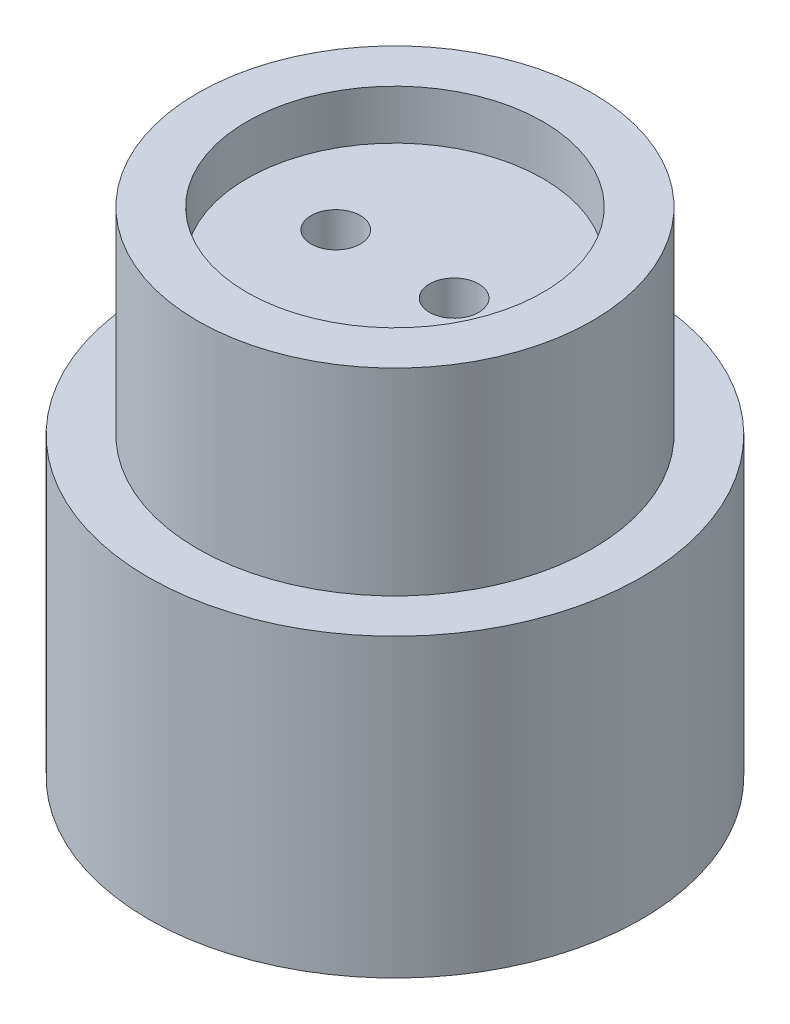
SolidWorks part; units mm, degrees
ref_plane "Front Plane" through (0, 0, 0) normal (0, 0, 1) x (1, 0, 0)
ref_plane "Top Plane" through (0, 0, 0) normal (0, 1, 0) x (1, 0, 0)
ref_plane "Right Plane" through (0, 0, 0) normal (1, 0, 0) x (0, 0, -1)
sketch "Sketch2" plane through (0, 0, 0) normal (0, 1, 0) x (1, 0, 0)
  circle A0 centre (0, 0) radius 25
  circle A1 centre (0, 0) radius 20
  dimension "D1" = 50
  dimension "D2" = 40
extrude "Boss-Extrude1" add sketch "Sketch2" along normal blind 30
extrude "Boss-Extrude2" add sketch "Sketch2<4>" along normal blind 50 separate body contours A1
sketch "Sketch2<4>" plane through (0, 0, 0) normal (0, 1, 0) x (1, 0, 0) same geometry as "Sketch2"
sketch "Sketch3" plane through (0, 0, 0) normal (0, 0, 1) x (1, 0, 0)
  line L0 (0, 50) -> (0, -6.482) construction
  line L1 (20, 50) -> (-20, 50) construction
  line L2 (-25, 30) -> (-25, 0) construction
  line L3 (-15, 42) -> (-9.5, 42)
  line L5 (-6, 45) -> (-6, 20)
  line L6 (-6, 20) -> (-13, 20)
  line L7 (-13, 20) -> (-13, 0)
  line L8 (25, 0) -> (-25, 0) construction
  line L14 (-9.5, 42) -> (-9.5, 23.5)
  line L15 (-20, 25) -> (-15, 25)
  line L16 (-15, 42) -> (-15, 25)
  line L19 (-9.5, 23.5) -> (-16.5, 23.5)
  line L22 (25, 30) -> (-25, 30) construction
  line L24 (-16.5, 23.5) -> (-16.5, 5)
  line L25 (-16.5, 5) -> (-20, 5)
  line L26 (-20, 25) -> (-20, 5)
  line L29 (-3.5, 45) -> (-3.5, 17.5) construction
  line L30 (-2.5, 42) -> (0, 42)
  line L31 (-2.5, 42) -> (-2.5, 16.5)
  line L32 (-2.5, 16.5) -> (0, 16.5)
  line L33 (0, 42) -> (0, 16.5)
  line L34 (-2.5, 42) -> (0, 16.5) construction
  line L35 (-2.5, 16.5) -> (0, 42) construction
  line L36 (-9.5, 16.5) -> (0, 16.5)
  line L37 (-9.5, 16.5) -> (-9.5, 5)
  line L38 (-9.5, 5) -> (0, 5)
  line L39 (0, 16.5) -> (0, 5)
  line L40 (-9.5, 16.5) -> (0, 5) construction
  line L41 (-9.5, 5) -> (0, 16.5) construction
  line L46 (-3.5, 17.5) -> (-10.5, 17.5) construction
  line L47 (-10.5, 17.5) -> (-10.5, 0) construction
  line L48 (-8.5, 45) -> (-8.5, 22.5) construction
  line L49 (-8.5, 22.5) -> (-15.5, 22.5) construction
  line L50 (-15.5, 22.5) -> (-15.5, 0) construction
  line L51 (-8.5, 45) -> (-3.5, 45) construction
  line L52 (-20, 50) -> (-20, 0) construction
  line L53 (-15, 50) -> (0, 50)
  line L54 (-15, 50) -> (-15, 45)
  line L55 (-15, 45) -> (0, 45)
  line L56 (0, 50) -> (0, 45)
  line L57 (-15, 50) -> (0, 45) construction
  line L58 (-15, 45) -> (0, 50) construction
  line L60 (13, 20) -> (13, 0) construction
  line L61 (6, 20) -> (13, 20) construction
  line L62 (6, 45) -> (6, 20) construction
  line L63 (10.5, 17.5) -> (10.5, 0) construction
  line L64 (15.5, 22.5) -> (15.5, 0) construction
  line L65 (8.5, 22.5) -> (15.5, 22.5) construction
  line L66 (3.5, 17.5) -> (10.5, 17.5) construction
  line L67 (3.5, 45) -> (3.5, 17.5) construction
  line L68 (8.5, 45) -> (3.5, 45) construction
  line L69 (8.5, 45) -> (8.5, 22.5) construction
  point P6 (-15.5, 24.531)
  point P8 (0, 0)
  point P31 (-1.25, 29.25)
  point P34 (-10.5, 8.75)
  point P35 (-4.75, 10.75)
  point P45 (-1.25, 42)
  point P49 (-7.5, 47.5)
  dimension "D1" = 20
  dimension "D2" = 7
  dimension "D3" = 25
  dimension "D4" = 6
  dimension "D5" = 5
  dimension "D6" = 8
  dimension "D7" = 2.5
  dimension "D8" = 2.5
  dimension "D9" = 1
  dimension "D10" = 1
  dimension "D11" = 1
  dimension "D12" = 1
  dimension "D13" = 1
  dimension "D14" = 1
  dimension "D15" = 5
  dimension "D16" = 5
  dimension "D17" = 5
revolve "Cut-Revolve1" cut sketch "Sketch3" angle 360 about L0
revolve "Cut-Revolve2" cut sketch "Sketch3<4>" angle 360 about L0
sketch "Sketch3<4>" plane through (0, 0, 0) normal (0, 0, 1) x (1, 0, 0) same geometry as "Sketch3"
revolve "Cut-Revolve3" cut sketch "Sketch3<5>" angle 360 about L0
sketch "Sketch3<5>" plane through (0, 0, 0) normal (0, 0, 1) x (1, 0, 0) same geometry as "Sketch3"
ref_plane "Plane1" through (0, 45, 0) normal (0, 1, 0) x (1, 0, 0)
sketch "Sketch4" plane through (0, 45, 0) normal (0, 1, 0) x (1, 0, 0)
  circle A0 centre (-6, 0) radius 2.5
sweep "Cut-Sweep1" cut profiles "Sketch4" path "Sketch3<10>"
sketch "Sketch3<10>" plane through (0, 0, 0) normal (0, 0, 1) x (1, 0, 0) same geometry as "Sketch3"
mirror "Mirror1" about plane through (0, 0, 0) normal (1, 0, 0) of "Cut-Sweep1"
